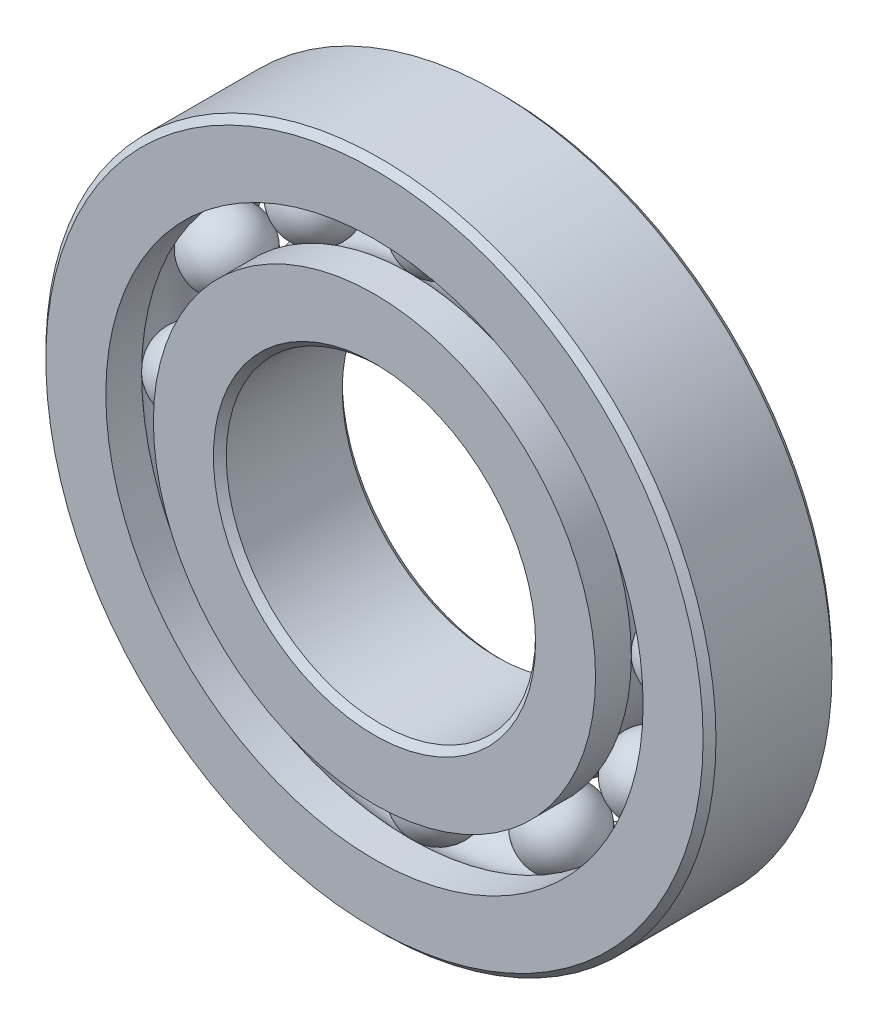
SolidWorks part; units mm, degrees
material "Plain Carbon Steel"
ref_plane "Front Plane" through (0, 0, 0) normal (0, 0, 1) x (1, 0, 0)
ref_plane "Top Plane" through (0, 0, 0) normal (0, 1, 0) x (1, 0, 0)
ref_plane "Right Plane" through (0, 0, 0) normal (1, 0, 0) x (0, 0, -1)
sketch "Sketch1" plane through (0, 0, 0) normal (1, 0, 0) x (0, 0, -1)
  line L0 (-3.9688, 0) -> (3.9688, 0) construction
  line L1 (0, 20.6375) -> (0, -20.6375) construction
  line L2 (3.5719, 20.6375) -> (-3.5719, 20.6375)
  line L3 (-3.5719, 20.6375) -> (-3.9688, 20.2406)
  line L4 (-3.9688, 20.2406) -> (-3.9688, 16.5466)
  line L5 (-3.9688, 16.5466) -> (-1.7639, 16.5466)
  line L6 (3.9687, 16.5466) -> (1.7639, 16.5466)
  line L7 (3.9687, 20.2406) -> (3.9687, 16.5466)
  line L8 (3.5719, 20.6375) -> (3.9687, 20.2406)
  line L9 (0, 20.6375) -> (0, 15.0813) construction
  line L10 (0, 15.0813) -> (0, 9.525) construction
  arc A0 (-1.7639, 16.5466) -> (1.7639, 16.5466) centre (0, 15.0813) cw
  point P14 (0, 9.525)
  dimension "D3" = 3.5278
  dimension "D1" = 45
  dimension "Width" = 7.9375
  dimension "OD" = 41.275
  dimension "D2" = 0.3969
  dimension "Shaft Dia" = 19.05
  dimension "D4" = 1.4654
revolve "Revolve1" add sketch "Sketch1" angle 360 about L0
sketch "Sketch3" plane through (0, 0, 0) normal (1, 0, 0) x (0, 0, -1)
  line L0 (-3.9688, 13.6159) -> (-1.7639, 13.6159)
  line L1 (0, 20.6375) -> (0, -20.6375) construction
  line L2 (-3.9688, 20.2406) -> (-3.9688, 16.5466) construction
  line L3 (-3.9688, 13.6159) -> (-3.9687, 9.9219)
  line L4 (-3.5719, 20.6375) -> (-3.9688, 20.2406) construction
  line L5 (-3.9687, 9.9219) -> (-3.5719, 9.525)
  line L6 (-3.5719, 9.525) -> (3.5719, 9.525)
  line L7 (3.5719, 20.6375) -> (3.5719, -20.6375) construction
  line L8 (3.5719, 9.525) -> (3.9687, 9.9219)
  line L9 (3.9687, -20.2406) -> (3.9687, 20.2406) construction
  line L10 (3.9687, 9.9219) -> (3.9688, 13.6159)
  line L11 (3.9688, 13.6159) -> (1.7639, 13.6159)
  line L13 (3.5719, 20.6375) -> (3.9687, 20.2406) construction
  arc A0 (1.7639, 16.5466) -> (-1.7639, 16.5466) centre (0, 15.0813) ccw construction
  arc A1 (1.7639, 13.6159) -> (-1.7639, 13.6159) centre (0, 15.0812) cw
revolve "Revolve3" add sketch "Sketch3" angle 360 about L0
sketch "Sketch4" plane through (0, 0, 0) normal (1, 0, 0) x (0, 0, -1)
  line L0 (-2.2932, 15.0813) -> (2.2932, 15.0813)
  arc A2 (-2.2932, 15.0813) -> (2.2932, 15.0813) centre (0, 15.0813) cw
  arc A3 (1.7639, 16.5466) -> (-1.7639, 16.5466) centre (0, 15.0813) ccw construction
revolve "Revolve4" add sketch "Sketch4" angle 360 about L0
ref_axis "Axis1" through (0, 0, -3.9688) along (0, 0, 1)
pattern_circular "CirPattern1" count 12 every 30 about axis through (0, 0, -3.9688) along (0, 0, 1) of bodies 104
equation "\"D2@Sketch1\" = \"Width@Sketch1\"*.05"
equation "\"D3@Sketch1\" = \"Width@Sketch1\"/2.25"
equation "\"D4@Sketch1\" = (((\"OD@Sketch1\"-\"Width@Sketch1\")/2)/3.25)/3.5"
equation "\"D2@CirPattern1\" = 360/\"Balls@CirPattern1\""
